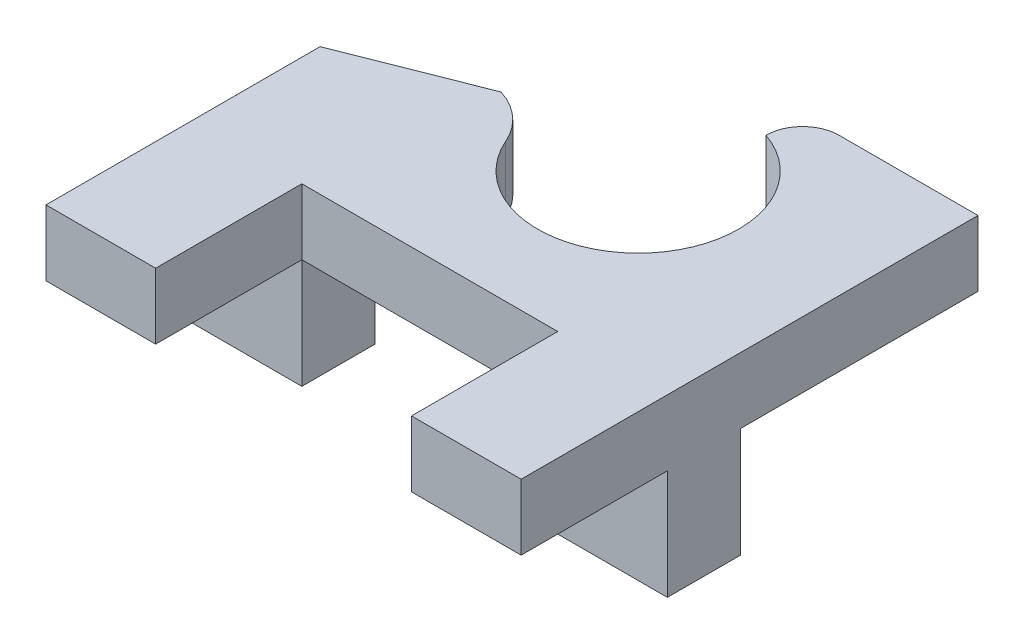
SolidWorks part; units mm, degrees
ref_plane "Front Plane" through (0, 0, 0) normal (0, 0, 1) x (1, 0, 0)
ref_plane "Top Plane" through (0, 0, 0) normal (0, 1, 0) x (1, 0, 0)
ref_plane "Right Plane" through (0, 0, 0) normal (1, 0, 0) x (0, 0, -1)
sketch "Sketch1" plane through (0, 0, 0) normal (0, 1, 0) x (1, 0, 0)
  line L0 (6.5, 2.5) -> (6.5, 0)
  line L1 (3.5, 0) -> (-3.5, 0)
  line L2 (-6.5, 0) -> (-6.5, 2.5)
  line L5 (-6.5, 2.5) -> (-6.5, 3.5)
  line L7 (6.5, 0) -> (6.5, -4)
  line L8 (6.5, -4) -> (3.5, -4)
  line L9 (3.5, 0) -> (3.5, -4)
  line L11 (-6.5, 0) -> (-6.5, -4)
  line L12 (-6.5, -4) -> (-3.5, -4)
  line L13 (-3.5, 0) -> (-3.5, -4)
  line L15 (6.5, 4.9) -> (6.5, 2.5)
  line L17 (-1.95, 4.9) -> (-2.95, 4.9)
  line L18 (-2.95, 4.9) -> (-6.5, 3.5)
  line L19 (1.7, 7.4986) -> (1.7, 8.4986)
  line L20 (1.7, 8.4986) -> (6.5, 8.4986)
  line L21 (6.5, 8.4986) -> (6.5, 4.9)
  arc A2 (-1.95, 4.9) -> (3.3581, 3.8908) centre (0.8, 4.9) ccw
  arc A3 (3.3581, 3.8908) -> (1.7, 7.4986) centre (0.8, 4.9) ccw
  point P0 (0, 0)
  dimension "D1" = 2.4
  dimension "D2" = 5.5
  dimension "D3" = 13
  dimension "D4" = 7.3
  dimension "D5" = 2.5
  dimension "D6" = 1
  dimension "D7" = 1
  dimension "D8" = 4
  dimension "D9" = 3
  dimension "D10" = 3.3
  dimension "D11" = 2.4
  dimension "D12" = 1
  dimension "D13" = 4.8
extrude "Boss-Extrude1" add sketch "Sketch1" along normal blind 1.8
fillet "Fillet1" radius 2 1 edges at (-1.95, 0.9, -4.9)
fillet "Fillet3" radius 1 1 edges at (1.7, 0.9, -8.4986)
ref_plane "Plane1" through (0, 0, 0) normal (0, -1, 0) x (-1, 0, 0)
sketch "Sketch2" plane through (0, 0, 0) normal (0, -1, 0) x (1, 0, 0)
  line L0 (6.5, 4) -> (6.5, -8.4986) construction
  line L1 (3.5, 0) -> (6.5, 0)
  line L2 (3.5, 0) -> (3.5, -2)
  line L3 (3.5, -2) -> (6.5, -2)
  line L4 (6.5, 0) -> (6.5, -2)
  line L5 (-6.5, -3.5) -> (-6.5, 4) construction
  line L6 (-3.5, 0) -> (-6.5, 0)
  line L7 (-3.5, 0) -> (-3.5, -2)
  line L8 (-3.5, -2) -> (-6.5, -2)
  line L9 (-6.5, 0) -> (-6.5, -2)
  dimension "D1" = 2
extrude "Boss-Extrude2" add sketch "Sketch2" along normal blind 3
